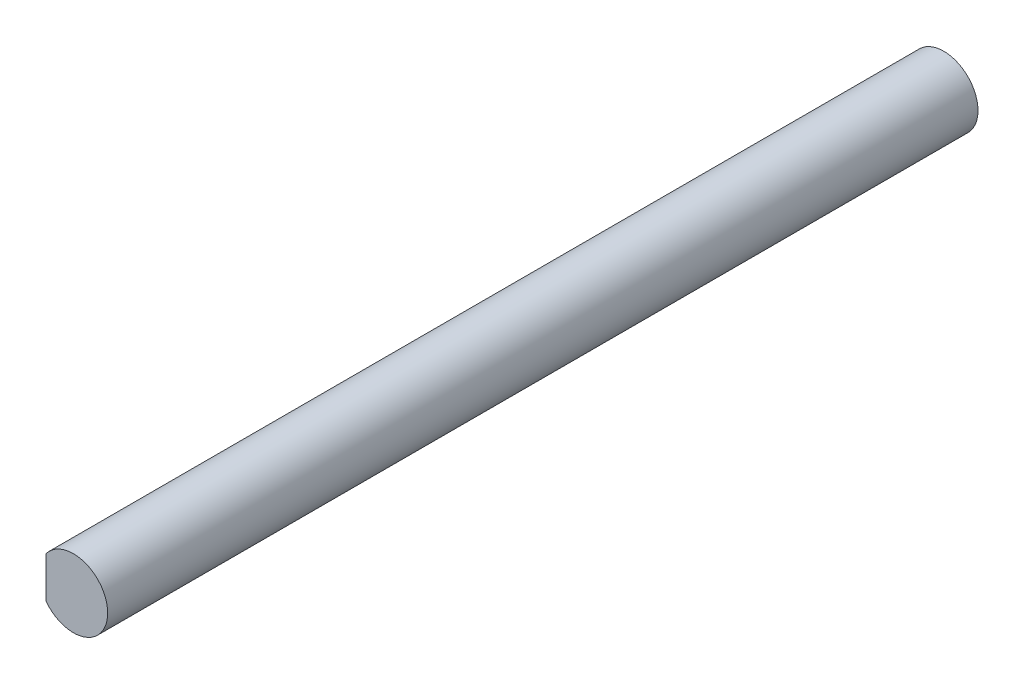
SolidWorks part; units mm, degrees
ref_plane "Front Plane" through (0, 0, 0) normal (0, 0, 1) x (1, 0, 0)
ref_plane "Top Plane" through (0, 0, 0) normal (0, 1, 0) x (1, 0, 0)
ref_plane "Right Plane" through (0, 0, 0) normal (1, 0, 0) x (0, 0, -1)
sketch "Sketch1" plane through (0, 0, 0) normal (0, 0, 1) x (1, 0, 0)
  line L2 (-2.4, 0) -> (-2.4, 1.8)
  line L3 (-2.4, 0) -> (-2.4, -1.8)
  arc A1 (-2.4, -1.8) -> (-2.4, 1.8) centre (0, 0) ccw
  dimension "D1" = 6
extrude "Boss-Extrude1" add sketch "Sketch1" along normal blind 76.2
